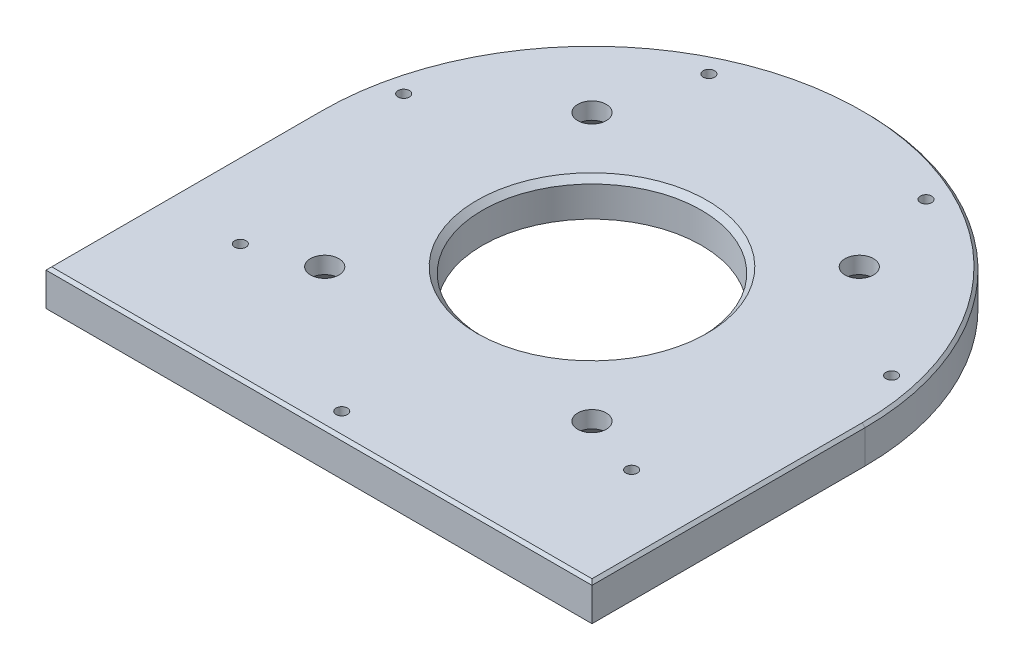
SolidWorks part; units mm, degrees
ref_plane "Front Plane" through (0, 0, 0) normal (0, 0, 1) x (1, 0, 0)
ref_plane "Top Plane" through (0, 0, 0) normal (0, 1, 0) x (1, 0, 0)
ref_plane "Right Plane" through (0, 0, 0) normal (1, 0, 0) x (0, 0, -1)
ref_axis "X Axis" through (-88.99, 0, 0) along (1, 0, 0)
ref_axis "Y Axiz" through (0, 0, 55) along (0, 0, -1)
ref_axis "Z Axis" through (0, 55, 0) along (0, -1, 0)
sketch "Sketch6" plane through (0, 0, 0) normal (0, 1, 0) x (1, 0, 0)
  line L0 (-48, 0) -> (-48, -48)
  line L1 (-48, -48) -> (48, -48)
  line L2 (48, -48) -> (48, 0)
  line L3 (48, 0) -> (-48, 0)
  dimension "D1" = 48
  dimension "D2" = 96
sketch "Sketch2" plane through (0, 0, 0) normal (0, 1, 0) x (1, 0, 0)
  line L0 (0, 0) -> (0, 35) construction
  line L1 (0, 0) -> (0, -44) construction
  line L2 (0, 0) -> (23.5, 23.5) construction
  circle A0 centre (0, 0) radius 48
  circle A1 centre (0, 35) radius 3 construction
  circle A27 centre (0, -44) radius 1
  circle A28 centre (-34.4006, -27.4336) radius 1
  circle A29 centre (-42.8968, 9.7909) radius 1
  circle A30 centre (-19.0909, 39.6426) radius 1
  circle A31 centre (19.0909, 39.6426) radius 1
  circle A32 centre (42.8968, 9.7909) radius 1
  circle A33 centre (34.4006, -27.4336) radius 1
  circle A43 centre (0, 0) radius 38 construction
  circle A45 centre (0, 0) radius 19.25
  circle A46 centre (0, 0) radius 32 construction
  circle A47 centre (23.5, 23.5) radius 2.5
  circle A48 centre (23.5, -23.5) radius 2.5
  circle A49 centre (-23.5, -23.5) radius 2.5
  circle A50 centre (-23.5, 23.5) radius 2.5
  circle A51 centre (0, 0) radius 33.234 construction
  point P19 (0, 0)
  point P38 (0, 0)
  point P51 (0, 0)
  point P54 (0, 0)
  point P59 (0, 0)
  dimension "D1" = 6
  dimension "D3" = 96
  dimension "D6" = 7
  dimension "D7" = 35
  dimension "D4" = 44
  dimension "D5" = 2
  dimension "D8" = 5
  dimension "D9" = 38.5
  dimension "D2" = 45
  dimension "D11" = 47
  dimension "D10" = 4
extrude "Boss-Extrude1" add sketch "Sketch6" along normal blind 6.35
extrude "Boss-Extrude2" add sketch "Sketch2" along normal blind 6.35
extrude "Cut-Extrude1" cut sketch "Sketch2<4>" along normal blind 6.35 contours A48 | A49 | A27 | A33 | A28 | A45
sketch "Sketch2<4>" plane through (0, 0, 0) normal (0, 1, 0) x (1, 0, 0) same geometry as "Sketch2"
chamfer "Chamfer1" distance 0.5 angle 45 4 edges at (-48, 6.35, 24) (0, 6.35, -48) (48, 6.35, 24) (0, 6.35, 48)
chamfer "Chamfer3" distance 1 angle 45 1 edges at (0, 6.35, 19.25)
chamfer "Chamfer5" distance 3.4 angle 45 4 edges at (23.5, 0, 26) (23.5, 0, -21) (-23.5, 0, -21) (-23.5, 0, 26)
